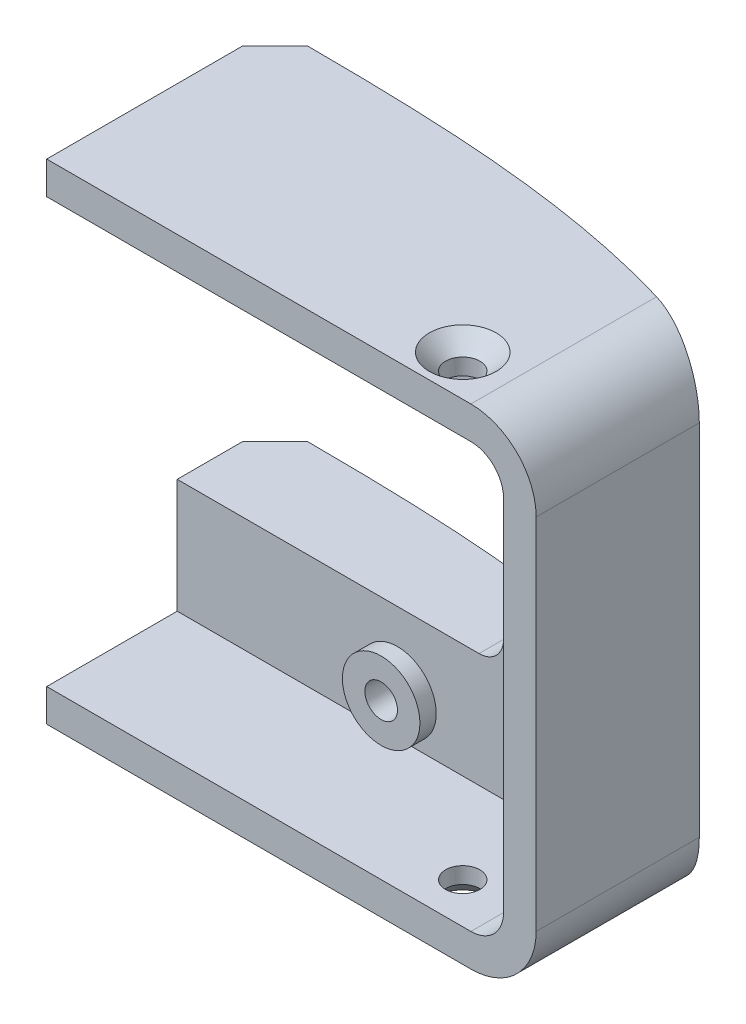
SolidWorks part; units mm, degrees
ref_plane "前视基准面" through (0, 0, 0) normal (0, 0, 1) x (1, 0, 0)
ref_plane "上视基准面" through (0, 0, 0) normal (0, 1, 0) x (1, 0, 0)
ref_plane "右视基准面" through (0, 0, 0) normal (1, 0, 0) x (0, 0, -1)
other "Configuration Table"
sketch "草图2" plane through (0, 0, 0) normal (0, 0, 1) x (1, 0, 0)
  line L1 (18.0576, 5.4113) -> (-11.9424, 5.4113)
  line L2 (18.0576, 5.4113) -> (18.0576, -24.5887)
  line L3 (18.0576, -24.5887) -> (-11.9424, -24.5887)
  line L4 (-11.9424, 5.4113) -> (-11.9424, -24.5887)
  dimension "D1" = 30
  dimension "D2" = 30
extrude "凸台-拉伸1" add sketch "草图2" against normal blind 10
shell "抽壳1" thickness 2 removed face at (-11.9424, -9.5887, -5)
sketch "草图3" plane through (0, 0, 0) normal (0, 0, 1) x (1, 0, 0)
  line L0 (-11.9424, 5.4113) -> (-11.9424, -24.5887) construction
  line L1 (-11.9424, -22.5887) -> (16.0576, -22.5887)
  line L2 (-11.9424, -22.5887) -> (-11.9424, 3.4113)
  line L3 (-11.9424, 3.4113) -> (16.0576, 3.4113)
  line L4 (16.0576, -22.5887) -> (16.0576, 3.4113)
  line L5 (16.0576, -22.5887) -> (16.0576, 3.4113) construction
extrude "切除-拉伸1" cut sketch "草图3" against normal up to next
sketch "草图4" plane through (0, -24.5887, 0) normal (0, -1, 0) x (1, 0, 0)
  line L1 (-11.9424, -10) -> (-11.9424, -14)
  line L2 (-11.9424, -10) -> (18.0576, -10)
  spline S0 degree 3 poles (-11.9424, -14) (-1.4718, -14.0066) (8.4407, -13.8133) (18.0576, -10) knots 0 0 0 0 1 1 1 1
  dimension "D1" = 4
extrude "凸台-拉伸2" add sketch "草图4" against normal up to surface (30 mm away) up to face at (3.0576, 5.4113, -5)
sketch "草图5" plane through (0, 0, 0) normal (0, 0, 1) x (1, 0, 0)
  line L0 (-11.9424, 3.4113) -> (-11.9424, -22.5887) construction
  line L1 (6.5576, -3.5887) -> (-11.9424, -3.5887)
  line L2 (8.0576, -5.0887) -> (8.0576, -14.0887)
  line L3 (6.5576, -15.5887) -> (-11.9424, -15.5887)
  line L4 (-11.9424, -3.5887) -> (-11.9424, -15.5887)
  line L6 (18.0576, -24.5887) -> (18.0576, 5.4113) construction
  arc A1 (8.0576, -14.0887) -> (6.5576, -15.5887) centre (6.5576, -14.0887) cw
  arc A2 (6.5576, -3.5887) -> (8.0576, -5.0887) centre (6.5576, -5.0887) cw
  point P9 (18.0576, -9.5887)
  point P10 (8.0576, -9.5887)
  point P19 (8.0576, -15.5887)
  point P22 (8.0576, -3.5887)
  dimension "D3" = 1.5
  dimension "D1" = 20
  dimension "D2" = 12
extrude "切除-拉伸2" cut sketch "草图5" against normal through all
sketch "草图6" plane through (0, 0, -8) normal (0, 0, 1) x (1, 0, 0)
  circle A0 centre (1.5576, 0.9087) radius 2.375
  circle A1 centre (14.0576, 0.9087) radius 2.375
  circle A2 centre (1.5576, -20.0913) radius 2.375
  circle A3 centre (14.0576, -20.0913) radius 2.375
extrude "凸台-拉伸3" add sketch "草图6" along normal blind 1
sketch "草图7" plane through (0, 0, -7) normal (0, 0, 1) x (1, 0, 0)
  circle A0 centre (1.5576, -20.0913) radius 1
  circle A1 centre (14.0576, -20.0913) radius 1
  circle A2 centre (1.5576, 0.9087) radius 1
  circle A3 centre (14.0576, 0.9087) radius 1
  dimension "D1" = 2
extrude "切除-拉伸3" cut sketch "草图7" against normal blind 3 draft 2
fillet "圆角2" radius 2 2 edges at (16.0576, -22.5887, -4) (16.0576, 3.4113, -4)
fillet "圆角3" radius 4 2 edges at (18.0576, -24.5887, -5) (18.0576, 5.4113, -5)
sketch "草图8" plane through (0, 5.4113, 0) normal (0, 1, 0) x (1, 0, 0)
  circle A0 centre (11.0576, 2.5) radius 1.05
  dimension "D1" = 2.1
extrude "切除-拉伸4" cut sketch "草图8" against normal through all
chamfer "倒角1" distance 1 angle 45 2 edges at (10.0076, -24.5887, -2.5) (10.0076, 5.4113, -2.5)
chamfer "倒角2" distance 2 angle 45 2 edges at (-11.9424, 0.9113, -14) (-11.9424, -20.0887, -14) first distance on face at (1.8442, -9.5131, -12.6965)
